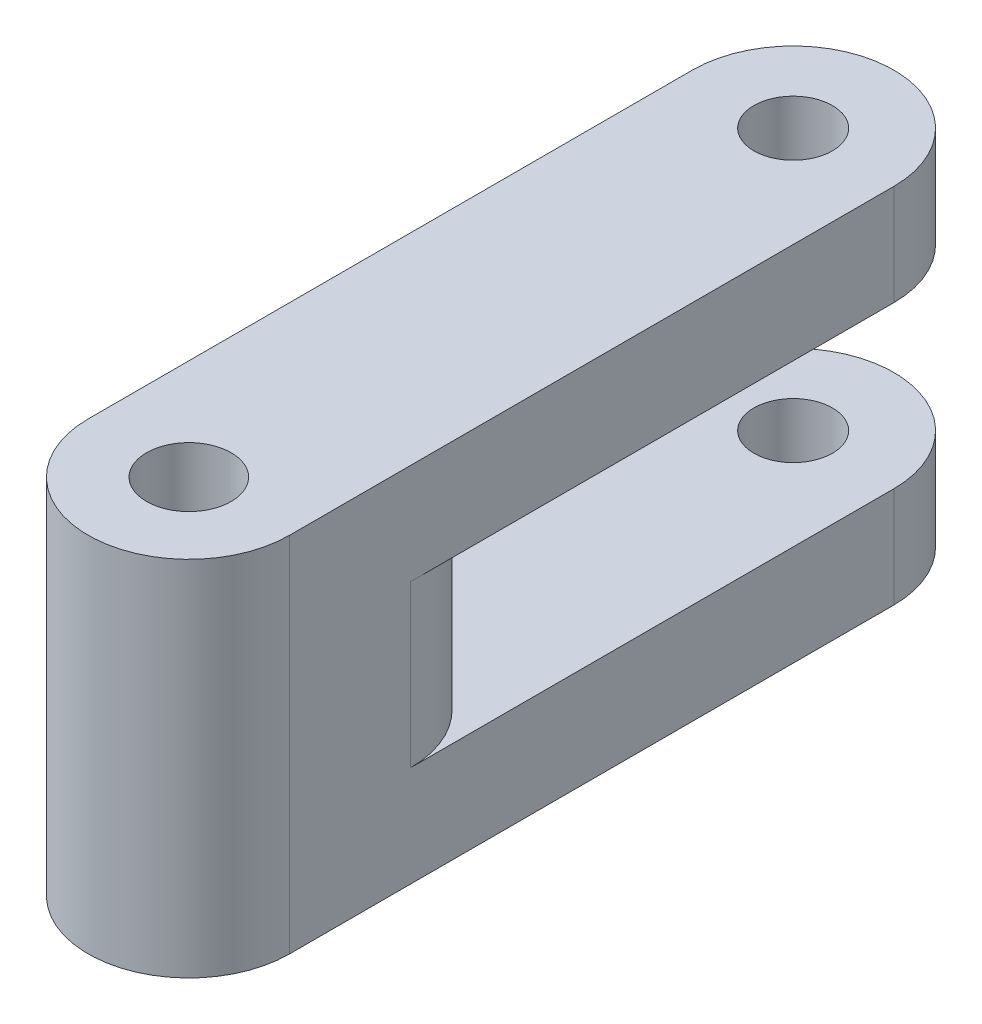
SolidWorks part; units mm, degrees
ref_plane "Plan de face" through (0, 0, 0) normal (0, 0, 1) x (1, 0, 0)
ref_plane "Plan de dessus" through (0, 0, 0) normal (0, 1, 0) x (1, 0, 0)
ref_plane "Plan de droite" through (0, 0, 0) normal (1, 0, 0) x (0, 0, -1)
sketch "Esquisse1" plane through (0, 0, 0) normal (0, 1, 0) x (1, 0, 0)
  line L0 (0, 0) -> (0, 30) construction
  line L1 (-5, 0) -> (-5, 30)
  line L2 (5, 0) -> (5, 30)
  arc A0 (-5, 0) -> (5, 0) centre (0, 0) ccw
  arc A1 (5, 30) -> (-5, 30) centre (0, 30) ccw
  circle A2 centre (0, 30) radius 1.95
  circle A3 centre (0, 0) radius 2.1
  point P3 (0, 15)
  dimension "D3" = 4.2
  dimension "D4" = 3.9
  dimension "D1" = 10
  dimension "D2" = 30
extrude "Boss.-Extru.1" add sketch "Esquisse1" along normal blind 5
sketch "Esquisse2" plane through (0, 5, 0) normal (0, 1, 0) x (1, 0, 0)
  line L0 (0, 0) -> (0, 6) construction
  line L1 (-5, 0) -> (-5, 6)
  line L2 (5, 0) -> (5, 6)
  arc A0 (-5, 0) -> (5, 0) centre (0, 0) ccw
  arc A1 (5, 6) -> (-5, 6) centre (0, 6) ccw
  arc A2 (-5, 0) -> (5, 0) centre (0, 0) ccw construction
  circle A3 centre (0, 0) radius 2.1 construction
  circle A4 centre (0, 0) radius 2.1
  point P3 (0, 3)
  dimension "D1" = 6
extrude "Boss.-Extru.2" add sketch "Esquisse2" along normal blind 8
sketch "Esquisse3" plane through (0, 5, 0) normal (0, 1, 0) x (1, 0, 0)
  line L0 (5, 0) -> (5, 6) construction
  line L1 (-5, 6) -> (-5, 0) construction
  line L2 (5, 6) -> (5, 30) construction
  line L3 (-5, 30) -> (-5, 6) construction
  line L4 (5, 0) -> (5, 6)
  line L5 (-5, 6) -> (-5, 0)
  line L6 (5, 6) -> (5, 30)
  line L7 (-5, 30) -> (-5, 6)
  arc A0 (-5, 0) -> (5, 0) centre (0, 0) ccw construction
  arc A1 (5, 6) -> (-5, 6) centre (0, 6) ccw construction
  arc A2 (5, 6) -> (-5, 6) centre (0, 6) ccw construction
  arc A3 (5, 30) -> (-5, 30) centre (0, 30) ccw construction
  arc A4 (-5, 0) -> (5, 0) centre (0, 0) ccw
  arc A5 (5, 6) -> (-5, 6) centre (0, 6) ccw
  arc A6 (5, 6) -> (-5, 6) centre (0, 6) ccw
  arc A7 (5, 30) -> (-5, 30) centre (0, 30) ccw
  circle A8 centre (0, 30) radius 1.95 construction
  circle A9 centre (0, 0) radius 2.1 construction
  circle A10 centre (0, 30) radius 1.95
  circle A11 centre (0, 0) radius 2.1
  arc M1 (-5, 6) -> (5, 6) centre (0, 6) cw
  line M2 (5, 6) -> (5, 30)
  arc M3 (5, 30) -> (-5, 30) centre (0, 30) ccw
  line M4 (-5, 30) -> (-5, 6)
  circle M5 centre (0, 30) radius 1.95
extrude "Boss.-Extru.3" add sketch "Esquisse3" along normal blind 5 from surface contours M4 M1 M2 M3 M5 | L5 A4 L4 A11 M1 region at (0, 5, -3.3333) region at (0, 5, -21.5041) starting at face at (0, 13, -3)
